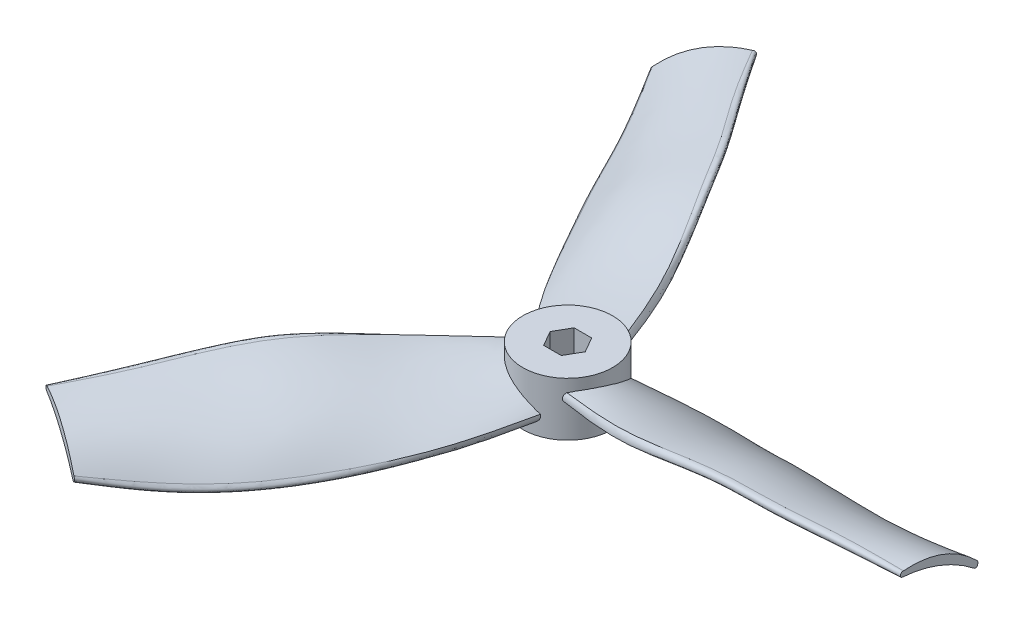
SolidWorks part; units mm, degrees
ref_plane "Front Plane" through (0, 0, 0) normal (0, 0, 1) x (1, 0, 0)
ref_plane "Top Plane" through (0, 0, 0) normal (0, 1, 0) x (1, 0, 0)
ref_plane "Right Plane" through (0, 0, 0) normal (1, 0, 0) x (0, 0, -1)
ref_plane "Plane1" through (2.4, 0, 0) normal (1, 0, 0) x (0, 0, -1)
sketch "1" plane through (2.4, 0, 0) normal (1, 0, 0) x (0, 0, -1)
  line L0 (0, 0) -> (-2.6, 0) construction
  line L1 (-3.2098, 1.0429) -> (3.2098, -1.0429) construction
  line L2 (-5, -2.6) -> (4, -2.6) construction
  line L3 (-5, 2.6) -> (4, 2.6) construction
  line L4 (0.0397, 0.1221) -> (0.3796, 1.1683) construction
  line L5 (-3.2229, 0.6792) -> (-3.0066, 1.3449) construction
  line L6 (3.0066, -1.3449) -> (3.2229, -0.6792) construction
  arc A0 (-3.0066, 1.3449) -> (3.2229, -0.6792) centre (-1.6427, -5.0558) cw
  arc A1 (-3.2229, 0.6792) -> (3.0066, -1.3449) centre (-3.4982, -10.7664) cw
  spline S0 degree 2 poles (-3.0066, 1.3449) (-3.3049, 1.0738) (-3.2229, 0.6792) knots 0 0 0 1 1 1
  spline S1 degree 2 poles (3.2229, -0.6792) (3.3049, -1.0738) (3.0066, -1.3449) knots 0 0 0 1 1 1
  point P11 (0.3796, 1.1683)
  point P20 (0.0397, 0.1221)
  dimension "D1" = 18
  dimension "D2" = 6.75
  dimension "D3" = 2.6
  dimension "D4" = 2.6
  dimension "D5" = 1.1
  dimension "D6" = 0.7
  dimension "D7" = 0.7
  dimension "D8" = 0.1
  dimension "D9" = 0.1
ref_plane "Plane2" through (9.7, 0, 0) normal (1, 0, 0) x (0, 0, -1)
sketch "2" plane through (9.7, 0, 0) normal (1, 0, 0) x (0, 0, -1)
  line L0 (4.4195, -1.7409) -> (-4.4195, 1.7409) construction
  line L1 (-4.1798, 2.0764) -> (-4.473, 1.3321) construction
  line L2 (0, 0) -> (-2.6, 0) construction
  line L3 (0.4146, 1.0525) -> (0.0481, 0.1221) construction
  line L4 (4.473, -1.3321) -> (4.1798, -2.0764) construction
  arc A0 (-4.1798, 2.0764) -> (4.473, -1.3321) centre (-5.1384, -13.0445) cw
  arc A1 (-4.473, 1.3321) -> (4.1798, -2.0764) centre (-8.0923, -20.5434) cw
  arc A2 (4.473, -1.3321) -> (4.1798, -2.0764) centre (3.6286, -1.4294) cw
  arc A3 (-4.1798, 2.0764) -> (-4.473, 1.3321) centre (-3.6286, 1.4294) ccw
  point P2 (0, 0)
  point P8 (-4.3264, 1.7042)
  point P13 (4.3264, -1.7042)
  point P17 (4.4195, -1.7409)
  point P19 (-4.4195, 1.7409)
  point P22 (0.4146, 1.0525)
  dimension "D1" = 9.5
  dimension "D2" = 21.5
  dimension "D3" = 1
  dimension "D4" = 0.1
  dimension "D5" = 0.8
  dimension "D6" = 0.8
  dimension "D7" = 0.1
ref_plane "Plane3" through (19.9, 0, 0) normal (1, 0, 0) x (0, 0, -1)
sketch "3" plane through (19.9, 0, 0) normal (1, 0, 0) x (0, 0, -1)
  line L0 (4.893, -2.325) -> (-4.893, 3.325) construction
  line L1 (0.4903, 0.8492) -> (0.9903, 1.7152) construction
  line L2 (0, 0) -> (-2.6, 0) construction
  line L3 (-4.7216, 2.8219) -> (-4.3716, 3.4281) construction
  line L4 (4.3716, -2.4281) -> (4.7216, -1.8219) construction
  line L5 (0, 0) -> (0, 0.5) construction
  line L6 (-5, -2.6) -> (4, -2.6) construction
  spline S0 degree 2 poles (-4.3716, 3.4281) (1.3965, 2.8691) (4.7216, -1.8219) knots 0 0 0 1 1 1
  spline S1 degree 2 poles (-4.7216, 2.8219) (0.7368, 1.7477) (4.3716, -2.4281) knots 0 0 0 1 1 1
  spline S2 degree 3 poles (-4.3716, 3.4281) (-4.6645, 3.4695) (-4.9641, 3.4714) (-4.9796, 2.8877) (-4.7216, 2.8219) knots 0 0 0 0 0.5 1 1 1 1
  spline S3 degree 3 poles (4.7216, -1.8219) (4.925, -2.0627) (5.0006, -2.2922) (4.6459, -2.6529) (4.3716, -2.4281) knots 0 0 0 0 0.5 1 1 1 1
  point P14 (-4.5466, 3.125)
  point P15 (4.5466, -2.125)
  point P20 (0, 0.5)
  dimension "D3" = 1
  dimension "D1" = 30
  dimension "D2" = 11.3
  dimension "D4" = 0.7
  dimension "D5" = 0.4
  dimension "D6" = 0.7
  dimension "D7" = 0.4
  dimension "D8" = 0.5
ref_plane "Plane4" through (24, 0, 0) normal (1, 0, 0) x (0, 0, -1)
ref_plane "Plane5" through (30, 0, 0) normal (1, 0, 0) x (0, 0, -1)
sketch "4" plane through (24, 0, 0) normal (1, 0, 0) x (0, 0, -1)
  line L0 (4.7631, -2.2) -> (-4.7631, 3.3) construction
  line L1 (-4.5917, 2.7969) -> (-4.2417, 3.4031) construction
  line L2 (0, 0) -> (-2.6, 0) construction
  line L3 (0.4358, 0.7548) -> (0.9358, 1.6209) construction
  line L4 (4.2417, -2.3031) -> (4.5917, -1.6969) construction
  line L5 (0, 0) -> (0, 0.55) construction
  spline S0 degree 2 poles (-4.2417, 3.4031) (1.2424, 2.6574) (4.5917, -1.6969) knots 0 0 0 1 1 1
  spline S1 degree 2 poles (-4.5917, 2.7969) (0.5824, 1.5356) (4.2417, -2.3031) knots 0 0 0 1 1 1
  spline S2 degree 3 poles (-4.2417, 3.4031) (-4.4613, 3.4253) (-4.8952, 3.4599) (-4.8008, 2.8549) (-4.5917, 2.7969) knots 0 0 0 0 0.5 1 1 1 1
  spline S3 degree 3 poles (4.5917, -1.6969) (4.7924, -1.9606) (4.8575, -2.1551) (4.5451, -2.5292) (4.2417, -2.3031) knots 0 0 0 0 0.5 1 1 1 1
  point P12 (4.4167, -2)
  point P13 (-4.4167, 3.1)
  point P20 (0, 0.55)
  dimension "D1" = 11
  dimension "D2" = 30
  dimension "D3" = 1
  dimension "D4" = 0.7
  dimension "D5" = 0.4
  dimension "D6" = 0.7
  dimension "D7" = 0.4
  dimension "D8" = 0.55
ref_plane "Plane6" through (36, 0, 0) normal (1, 0, 0) x (0, 0, -1)
sketch "5" plane through (30, 0, 0) normal (1, 0, 0) x (0, 0, -1)
  line L0 (4.1982, -1.5271) -> (-4.1982, 3.1271) construction
  line L1 (-4.018, 2.627) -> (-3.6786, 3.2393) construction
  line L2 (0.1654, 1.0984) -> (0.6502, 1.973) construction
  line L3 (3.6786, -1.6393) -> (4.018, -1.027) construction
  line L4 (0, 0) -> (0, 0.8) construction
  line L5 (0, 0) -> (-2.6, 0) construction
  spline S0 degree 2 poles (-3.6786, 3.2393) (1.1307, 2.8399) (4.018, -1.027) knots 0 0 0 1 1 1
  spline S1 degree 2 poles (-4.018, 2.627) (0.5005, 1.7029) (3.6786, -1.6393) knots 0 0 0 1 1 1
  spline S2 degree 3 poles (-3.6786, 3.2393) (-3.8982, 3.2615) (-4.3337, 3.2809) (-4.2271, 2.6851) (-4.018, 2.627) knots 0 0 0 0 0.5 1 1 1 1
  spline S3 degree 3 poles (4.018, -1.027) (4.2187, -1.2907) (4.296, -1.4761) (3.982, -1.8654) (3.6786, -1.6393) knots 0 0 0 0 0.5 1 1 1 1
  point P9 (3.8483, -1.3332)
  point P10 (-3.8483, 2.9332)
  point P16 (0, 0.8)
  dimension "D1" = 9.6
  dimension "D2" = 1
  dimension "D3" = 0.7
  dimension "D4" = 0.4
  dimension "D5" = 0.7
  dimension "D6" = 0.4
  dimension "D7" = 0.8
  dimension "D8" = 29
sketch "6" plane through (36, 0, 0) normal (1, 0, 0) x (0, 0, -1)
  line L0 (3.7343, 0.0665) -> (-3.7343, 2.9335) construction
  line L1 (-0.7, 2.9) -> (-0.9867, 2.1531) construction
  line L2 (0, 0) -> (-2.6, 0) construction
  line L3 (-3.458, 3.0952) -> (-3.6372, 2.6284) construction
  line L4 (3.6551, 0.4183) -> (3.4401, -0.1419) construction
  line L5 (0, 1.5) -> (0, 0) construction
  spline S0 degree 2 poles (-3.458, 3.0952) (0.5989, 3.4075) (3.6551, 0.4183) knots 0 0 0 1 1 1
  spline S1 degree 2 poles (-3.6372, 2.6284) (0.272, 2.3328) (3.4401, -0.1419) knots 0 0 0 1 1 1
  spline S2 degree 3 poles (-3.458, 3.0952) (-3.6046, 3.1125) (-3.7858, 2.9673) (-3.7612, 2.6868) (-3.6372, 2.6284) knots 0 0 0 0 0.5 1 1 1 1
  spline S3 degree 3 poles (3.6551, 0.4183) (3.7925, 0.2475) (3.7429, 0.1038) (3.659, -0.189) (3.4401, -0.1419) knots 0 0 0 0 0.5 1 1 1 1
  point P13 (-3.5476, 2.8618)
  point P27 (0, 1.5)
  point P28 (3.5476, 0.1382)
  dimension "D1" = 8
  dimension "D2" = 21
  dimension "D3" = 0.8
  dimension "D4" = 0.5
  dimension "D5" = 0.2
  dimension "D6" = 0.6
  dimension "D7" = 0.2
  dimension "D8" = 1.5
loft "Loft1" add profiles "1", "Sketch6<3>", "3", "4", "5", "6" connector at (2.4, 1.3449, 3.0066) connector at (9.7, 2.0764, 4.1798) connector at (19.9, 3.4281, 4.3716) connector at (24, 3.4031, 4.2417) connector at (30, 3.2393, 3.6786) connector at (36, 3.0952, 3.458)
sketch "Sketch6<3>" plane through (9.7, 0, 0) normal (1, 0, 0) x (0, 0, -1) same geometry as "2"
sketch "Sketch11" plane through (0, 0, 0) normal (0, 1, 0) x (1, 0, 0)
  circle A0 centre (0, 0) radius 4.35
  dimension "D1" = 8.7
extrude "Boss-Extrude3" add sketch "Sketch11" along normal blind 2.6 and the other way blind 2.6 separate body
sketch "Sketch12" plane through (0, 0, 0) normal (0, 1, 0) x (1, 0, 0)
  line L1 (0.8516, 1.475) -> (-0.8516, 1.475)
  line L2 (-0.8516, 1.475) -> (-1.7032, 0)
  line L3 (-1.7032, 0) -> (-0.8516, -1.475)
  line L4 (-0.8516, -1.475) -> (0.8516, -1.475)
  line L5 (0.8516, -1.475) -> (1.7032, 0)
  line L6 (1.7032, 0) -> (0.8516, 1.475)
  circle A0 centre (0, 0) radius 1.475 construction
  dimension "D1" = 2.95
extrude "Cut-Extrude1" cut sketch "Sketch12" against normal blind 2.6 and the other way blind 2.6
ref_axis "Axis1" through (0, 4.4, 0) along (0, -1, 0)
pattern_circular "CirPattern1" count 3 over 360 about axis through (0, 4.4, 0) along (0, -1, 0) of bodies 101
ref_plane "Bottom" through (0, -2.6, 0) normal (0, -1, 0) x (-1, 0, 0)
